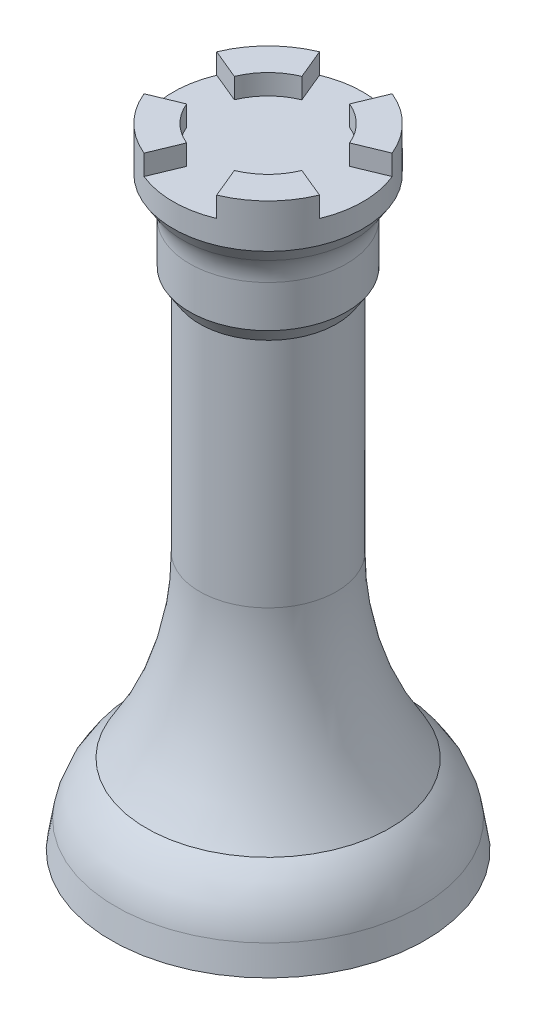
SolidWorks part; units mm, degrees
ref_plane "Front Plane" through (0, 0, 0) normal (0, 0, 1) x (1, 0, 0)
ref_plane "Top Plane" through (0, 0, 0) normal (0, 1, 0) x (1, 0, 0)
ref_plane "Right Plane" through (0, 0, 0) normal (1, 0, 0) x (0, 0, -1)
sketch "Sketch1" plane through (0, 0, 0) normal (0, 0, 1) x (1, 0, 0)
  line L21 (4.5897, -9.2849) -> (-7.0103, -9.2849)
  line L22 (-6.678, -7.2849) -> (-7.0103, -9.2849)
  line L23 (4.5897, 35.7151) -> (4.5897, -9.2849)
  line L25 (4.5897, -9.2849) -> (4.5897, 40.7151) construction
  line L26 (-1.2092, 28.0478) -> (-0.4727, 26.9092)
  line L27 (-0.0203, 35.7151) -> (4.5897, 35.7151)
  line L28 (-0.4727, 26.9092) -> (-0.4727, 9.7789)
  line L29 (-0.0203, 35.7151) -> (-0.0203, 37.2151)
  line L30 (-0.0203, 37.2151) -> (-2.4303, 37.2151)
  line L33 (-2.4303, 33.9851) -> (-1.735, 32.9104)
  line L34 (-1.2092, 31.1297) -> (-1.2092, 28.0478)
  line L36 (-2.4303, 33.9851) -> (-2.4303, 35.7151)
  line L37 (-2.4303, 37.2151) -> (-2.4303, 35.7151)
  line L38 (-0.0203, 35.7151) -> (-2.4303, 35.7151)
  arc A6 (-4.4103, -3.4011) -> (-6.678, -7.2849) centre (-0.4448, -8.3205) ccw
  arc A8 (-1.735, 32.9104) -> (-1.2092, 31.1297) centre (-4.4875, 31.1297) cw
  arc A9 (-0.4727, 9.7789) -> (-4.4103, -3.4011) centre (-24.4993, 9.7789) cw
  point P2 (-0.4727, 9.7789)
  dimension "D6" = 11.6
  dimension "D11" = 6.3187
  dimension "D14" = 4.61
  dimension "D18" = 3.23
  dimension "D22" = 3.2783
  dimension "D2" = 2
  dimension "D3" = 1.5
  dimension "D7" = 45
  dimension "D8" = 5.8838
  dimension "D12" = 9
  dimension "D16" = 2.41
  dimension "D17" = 1.28
  dimension "D21" = 5.7989
revolve "Revolve5" add sketch "Sketch1" angle 360 about L25 region at (1.1021, 10.7577, 0) region at (-1.2253, 36.4651, 0)
revolve "Cut-Revolve1" cut sketch "Sketch1<3>" angle 45 mid plane about L25 region at (-1.2253, 36.4651, 0)
sketch "Sketch1<3>" plane through (0, 0, 0) normal (0, 0, 1) x (1, 0, 0) same geometry as "Sketch1"
pattern_circular "CirPattern1" count 4 every 90 about axis through (4.5897, -9.2849, 0) along (0, 1, 0) of "Cut-Revolve1"
